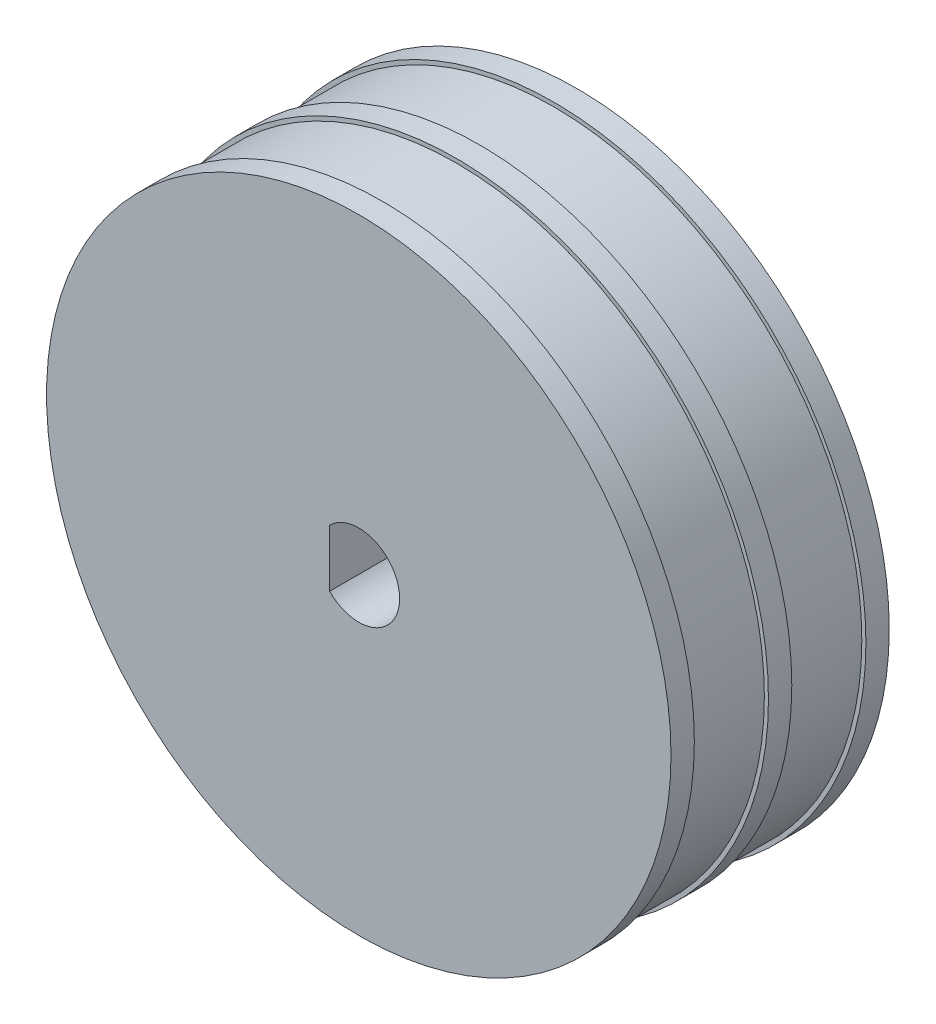
SolidWorks part; units mm, degrees
material "ABS"
ref_plane "Front Plane" through (0, 0, 0) normal (0, 0, 1) x (1, 0, 0)
ref_plane "Top Plane" through (0, 0, 0) normal (0, 1, 0) x (1, 0, 0)
ref_plane "Right Plane" through (0, 0, 0) normal (1, 0, 0) x (0, 0, -1)
sketch "Sketch2" plane through (0, 0, 0) normal (0, 0, 1) x (1, 0, 0)
  circle A0 centre (0, 0) radius 13.375
  dimension "D1" = 26.75
extrude "Boss-Extrude1" add sketch "Sketch2" along normal blind 1
sketch "Sketch3" plane through (0, 0, 1) normal (0, 0, 1) x (1, 0, 0)
  circle A0 centre (0, 0) radius 13.2
  dimension "D1" = 26.4
extrude "Boss-Extrude2" add sketch "Sketch3" along normal blind 3.175
sketch "Sketch4" plane through (0, 0, 4.175) normal (0, 0, 1) x (1, 0, 0)
  circle A0 centre (0, 0) radius 13.375 construction
  circle A1 centre (0, 0) radius 13.375
extrude "Boss-Extrude3" add sketch "Sketch4" along normal blind 1
sketch "Sketch5" plane through (0, 0, 5.175) normal (0, 0, 1) x (1, 0, 0)
  circle A0 centre (0, 0) radius 13.2 construction
  circle A1 centre (0, 0) radius 13.2
extrude "Boss-Extrude4" add sketch "Sketch5" along normal blind 3.175
sketch "Sketch6" plane through (0, 0, 8.35) normal (0, 0, 1) x (1, 0, 0)
  circle A0 centre (0, 0) radius 13.375 construction
  circle A1 centre (0, 0) radius 13.375
extrude "Boss-Extrude5" add sketch "Sketch6" along normal blind 1
sketch "Sketch7" plane through (0, 0, 9.35) normal (0, 0, 1) x (1, 0, 0)
  line L0 (-1, 1.118) -> (-1, -1.118)
  line L1 (0, 0) -> (0, 13.375) construction
  line L2 (0, 0) -> (13.375, 0) construction
  line L3 (0.5, 0.5) -> (0.5, 10.5)
  line L4 (0.5, 0.5) -> (10.5, 0.5)
  line L5 (10.5, 0.5) -> (0.5, 10.5)
  line L6 (0.5, 11.2389) -> (11.2389, 0.5)
  line L7 (11.2389, -0.5) -> (0.5, -11.2389)
  line L8 (0.5, -10.5) -> (10.5, -0.5)
  line L9 (0.5, -0.5) -> (10.5, -0.5)
  line L10 (0.5, -0.5) -> (0.5, -10.5)
  line L11 (-0.5, -11.2389) -> (-11.2389, -0.5)
  line L12 (-10.5, -0.5) -> (-0.5, -10.5)
  line L13 (-0.5, -0.5) -> (-0.5, -10.5)
  line L14 (-0.5, -0.5) -> (-10.5, -0.5)
  line L15 (-11.2389, 0.5) -> (-0.5, 11.2389)
  line L16 (-0.5, 10.5) -> (-10.5, 0.5)
  line L17 (-0.5, 0.5) -> (-10.5, 0.5)
  line L18 (-0.5, 0.5) -> (-0.5, 10.5)
  line L23 (-6.3998, 5.3391) -> (-5.3391, 6.3998)
  line L27 (1.156, 2.2167) -> (2.2167, 1.156)
  line L28 (1.156, 2.2167) -> (8.0801, 9.1407)
  line L29 (2.2167, 1.156) -> (9.1407, 8.0801)
  line L30 (8.0801, 9.1407) -> (9.1407, 8.0801)
  line L31 (2.2167, -1.156) -> (1.156, -2.2167)
  line L32 (2.2167, -1.156) -> (9.1407, -8.0801)
  line L33 (9.1407, -8.0801) -> (8.0801, -9.1407)
  line L34 (1.156, -2.2167) -> (8.0801, -9.1407)
  line L35 (-1.156, -2.2167) -> (-2.2167, -1.156)
  line L36 (-1.156, -2.2167) -> (-8.0801, -9.1407)
  line L37 (-8.0801, -9.1407) -> (-9.1407, -8.0801)
  line L38 (-2.2167, -1.156) -> (-9.1407, -8.0801)
  line L39 (-2.2167, 1.156) -> (-1.156, 2.2167)
  line L40 (-2.2167, 1.156) -> (-9.1407, 8.0801)
  line L41 (-9.1407, 8.0801) -> (-8.0801, 9.1407)
  line L42 (-1.156, 2.2167) -> (-8.0801, 9.1407)
  arc A0 (-1, -1.118) -> (-1, 1.118) centre (0, 0) ccw
  circle A1 centre (0, 0) radius 2.5
  circle A2 centre (0, 0) radius 13.375 construction
  circle A3 centre (0, 0) radius 12.2
  circle A4 centre (0, 0) radius 12.2
  arc A5 (11.2389, 0.5) -> (0.5, 11.2389) centre (0, 0) ccw
  arc A6 (0.5, -11.2389) -> (11.2389, -0.5) centre (0, 0) ccw
  arc A7 (-11.2389, -0.5) -> (-0.5, -11.2389) centre (0, 0) ccw
  arc A8 (-0.5, 11.2389) -> (-11.2389, 0.5) centre (0, 0) ccw
  point P13 (0.5, 0.5)
  point P14 (-5.8694, 5.8694)
  point P37 (0, 0)
  point P38 (-5.8694, 5.8694)
  point P56 (0, 0)
  point P59 (0, 0)
  dimension "D1" = 3
  dimension "D4" = 5
  dimension "D8" = 22.5
  dimension "D2" = 1
  dimension "D5" = 0.5
  dimension "D6" = 0.5
  dimension "D7" = 10
  dimension "D10" = 1.5
  dimension "D3" = 1
  dimension "D9" = 4
  dimension "D11" = 4
extrude "Cut-Extrude1" [suppressed] cut sketch "Sketch7" against normal blind 10 contours L40 A8 L15 | L15 A8 L42 | A1 L18 L16 L42 | A1 L40 L16 L17 | A1 L14 L12 L38 | L11 A7 L38 | L36 A7 L11 | A1 L36 L12 L13 | A1 L10 L8 L34 | A1 L32 L8 L9 | A1 L4 L5 L29 | A1 L28 L5 L3 | L28 A5 L6 | L6 A5 L29 | L32 A6 L7 | L7 A6 L34 | L3 A0 L18 L17 L0 L14 L13 L10 L9 L4 | L4 A0 L3 | L18 A0 L0 L17 | L0 A0 L13 L14 | L10 A0 L9
sketch "Sketch8" plane through (0, 0, 0) normal (0, 0, -1) x (-1, 0, 0)
  line L0 (1, 1.118) -> (1, -1.118) construction
  line L1 (1.25, 1.2247) -> (1.25, -1.2247)
  arc A1 (1, 1.118) -> (1, -1.118) centre (0, 0) ccw construction
  arc A2 (1.25, 1.2247) -> (1.25, -1.2247) centre (0, 0) ccw
  dimension "D1" = 0.25
  dimension "D2" = 3
  dimension "D3" = 1
extrude "Cut-Extrude2" cut sketch "Sketch8" against normal through all
